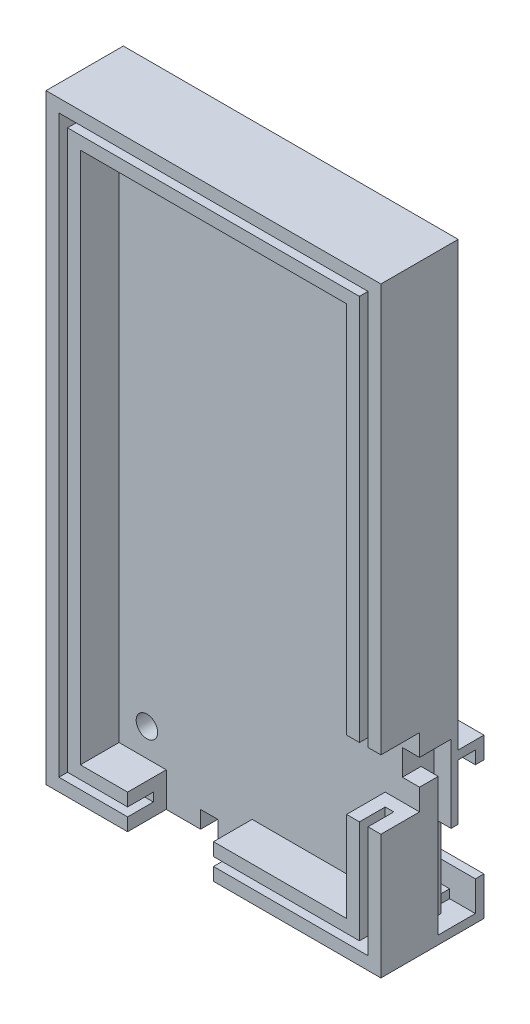
SolidWorks part; units mm, degrees
ref_plane "Front Plane" through (0, 0, 0) normal (0, 0, 1) x (1, 0, 0)
ref_plane "Top Plane" through (0, 0, 0) normal (0, 1, 0) x (1, 0, 0)
ref_plane "Right Plane" through (0, 0, 0) normal (1, 0, 0) x (0, 0, -1)
sketch "Sketch1" plane through (0, 0, 0) normal (0, 0, 1) x (1, 0, 0)
  line L1 (0, 0) -> (39, 0)
  line L2 (0, 0) -> (0, 70)
  line L3 (0, 70) -> (39, 70)
  line L4 (39, 0) -> (39, 70)
  dimension "D1" = 70
  dimension "D2" = 39
extrude "Boss-Extrude1" add sketch "Sketch1" along normal blind 4.5
sketch "Sketch2" plane through (0, 0, 4.5) normal (0, 0, 1) x (1, 0, 0)
  line L0 (0, 70) -> (0, 0) construction
  line L1 (39, 70) -> (0, 70)
  line L2 (39, 70) -> (39, 66)
  line L3 (39, 66) -> (0, 66)
  line L4 (0, 70) -> (0, 66)
  line L5 (0, 0) -> (39, 0) construction
  line L6 (0, 66) -> (4, 66)
  line L7 (0, 66) -> (0, 0)
  line L8 (0, 0) -> (4, 0)
  line L9 (4, 66) -> (4, 0)
  line L10 (39, 0) -> (39, 70) construction
  line L11 (4, 0) -> (39, 0)
  line L12 (4, 0) -> (4, 4)
  line L13 (4, 4) -> (39, 4)
  line L14 (39, 0) -> (39, 4)
  line L16 (39, 66) -> (35, 66)
  line L17 (39, 66) -> (39, 4)
  line L18 (39, 4) -> (35, 4)
  line L19 (35, 66) -> (35, 4)
  line M6 (0, 70) -> (0, 0)
  line M7 (0, 0) -> (39, 0)
  line M8 (39, 0) -> (39, 70)
  line M9 (39, 70) -> (0, 70)
  dimension "D1" = 4
  dimension "D2" = 4
  dimension "D3" = 4
  dimension "D4" = 4
extrude "Boss-Extrude2" add sketch "Sketch2" along normal blind 4.5 contours L3 M8 M9 M6 | L3 L19 L13 M8 | L9 L3 M6 M7 | L13 L9 M7 M8 region at (19.5, 68, 4.5) region at (37, 35, 4.5) region at (2, 33, 4.5) region at (21.5, 2, 4.5)
sketch "Sketch3" plane through (0, 4, 0) normal (0, 1, 0) x (1, 0, 0)
  line L0 (4, -4.5) -> (35, -4.5) construction
  line L1 (9.5, -4.5) -> (19.5, -4.5)
  line L2 (9.5, -4.5) -> (9.5, -9)
  line L3 (9.5, -9) -> (19.5, -9)
  line L4 (19.5, -4.5) -> (19.5, -9)
  line L5 (4, -9) -> (35, -9) construction
  line L6 (4, -9) -> (4, -4.5) construction
  dimension "D1" = 5.5
  dimension "D2" = 15.5
extrude "Cut-Extrude1" cut sketch "Sketch3" against normal blind 4
sketch "Sketch4" plane through (35, 0, 0) normal (-1, 0, 0) x (0, 0, 1)
  line L0 (4.5, 66) -> (4.5, 4) construction
  line L1 (4.5, 14.5) -> (9, 14.5)
  line L2 (4.5, 14.5) -> (4.5, 22.5)
  line L3 (4.5, 22.5) -> (9, 22.5)
  line L4 (9, 14.5) -> (9, 22.5)
  line L5 (9, 66) -> (9, 4) construction
  line L6 (9, 4) -> (4.5, 4) construction
  dimension "D1" = 10.5
  dimension "D2" = 18.5
extrude "Cut-Extrude2" cut sketch "Sketch4" against normal blind 4
sketch "Sketch5" plane through (0, 0, 4.5) normal (0, 0, 1) x (1, 0, 0)
  line L0 (4, 4) -> (9.5, 4) construction
  line L1 (4, 66) -> (4, 4) construction
  line L2 (19.5, 66) -> (19.5, 4) construction
  line L3 (35, 66) -> (4, 66) construction
  line L5 (19.5, 35) -> (4, 35) construction
  line L6 (4, 66) -> (4, 4) construction
  circle A0 centre (7.25, 7.25) radius 1.25
  circle A1 centre (31.75, 7.25) radius 1.25
  circle A2 centre (7.25, 62.75) radius 1.25
  dimension "D1" = 3.25
  dimension "D3" = 2.5
  dimension "D2" = 3.25
extrude "Cut-Extrude3" cut sketch "Sketch5" against normal blind 4
sketch "Sketch7" plane through (0, 0, 0) normal (0, 0, -1) x (-1, 0, 0)
  line L0 (-39, 0) -> (-39, 18.5) construction
  line L1 (-39, 0) -> (-39, 70) construction
  line L3 (-39, 1) -> (-8, 1)
  line L4 (-39, 1) -> (-39, 17.5)
  line L5 (-39, 17.5) -> (-8, 17.5)
  line L6 (-8, 1) -> (-8, 17.5)
  line L9 (0, 0) -> (-39, 0) construction
  line L10 (-39, 0) -> (-7, 0)
  line L11 (-7, 0) -> (-7, 18.5)
  line L12 (-7, 18.5) -> (-39, 18.5)
  line L13 (-39, 18.5) -> (-39, 17.5)
  line L14 (-39, 1) -> (-39, 0)
  line M8 (-39, 70) -> (-39, 0)
  line M9 (-39, 0) -> (0, 0)
  dimension "D1" = 18.5
  dimension "D2" = 1
  dimension "D3" = 16.5
  dimension "D4" = 31
  dimension "D5" = 32
  dimension "D6" = 18.5
extrude "Boss-Extrude3" add sketch "Sketch7" along normal blind 3 contours L11 L12 L5 L6 L3 M8 M9 region at (23.5, 0.6304, 0)
sketch "Sketch8" plane through (8, 0, 0) normal (1, 0, 0) x (0, 0, -1)
  line L0 (3, 17.5) -> (0, 17.5) construction
  line L1 (1, 17.5) -> (2, 17.5)
  line L2 (1, 17.5) -> (1, 16.5)
  line L3 (1, 16.5) -> (2, 16.5)
  line L4 (2, 17.5) -> (2, 16.5)
  line L5 (0, 1) -> (0, 17.5) construction
  line L6 (0, 9.25) -> (3, 9.25) construction
  line L7 (3, 1) -> (3, 17.5) construction
  line L8 (1, 2) -> (2, 2)
  line L9 (2, 1) -> (2, 2)
  line L10 (1, 1) -> (2, 1)
  line L11 (1, 1) -> (1, 2)
  dimension "D1" = 1
  dimension "D2" = 1
  dimension "D3" = 1
extrude "Boss-Extrude4" add sketch "Sketch8" along normal blind 28
sketch "Sketch9" plane through (8, 0, 0) normal (1, 0, 0) x (0, 0, -1)
  line L1 (3, 1) -> (2, 1)
  line L2 (3, 1) -> (3, 17.5)
  line L3 (3, 17.5) -> (2, 17.5)
  line L4 (2, 1) -> (2, 17.5)
extrude "Boss-Extrude5" add sketch "Sketch9" along normal blind 14
sketch "Sketch10" plane through (22, 0, 0) normal (1, 0, 0) x (0, 0, -1)
  line L0 (3, 1) -> (3, 17.5) construction
  line L1 (2, 17.5) -> (3, 17.5)
  line L2 (2, 17.5) -> (2, 16)
  line L3 (2, 16) -> (3, 16)
  line L4 (3, 17.5) -> (3, 16)
  line L6 (2, 1) -> (3, 1)
  line L7 (2, 1) -> (2, 4.5)
  line L8 (2, 4.5) -> (3, 4.5)
  line L9 (3, 1) -> (3, 4.5)
  dimension "D1" = 1.5
  dimension "D2" = 3.5
extrude "Boss-Extrude6" add sketch "Sketch10" along normal blind 17
sketch "Sketch11" plane through (0, 0, 0) normal (0, 0, -1) x (-1, 0, 0)
  line L0 (0, 0) -> (-7, 0) construction
  line L1 (-4, 0) -> (-5, 0)
  line L2 (-4, 0) -> (-4, 21.5)
  line L3 (-4, 21.5) -> (-5, 21.5)
  line L4 (-5, 0) -> (-5, 21.5)
  line L5 (-7, 0) -> (-7, 18.5) construction
  line L7 (0, 70) -> (0, 0) construction
  line L8 (-5, 21.5) -> (-22, 21.5)
  line L9 (-5, 21.5) -> (-5, 20.5)
  line L10 (-5, 20.5) -> (-22, 20.5)
  line L11 (-22, 21.5) -> (-22, 20.5)
  line L12 (-7, 18.5) -> (-39, 18.5) construction
  line L13 (-28, 18.5) -> (-27, 18.5)
  line L14 (-28, 18.5) -> (-28, 21.5)
  line L15 (-28, 21.5) -> (-27, 21.5)
  line L16 (-27, 18.5) -> (-27, 21.5)
  line M5 (-7, 0) -> (0, 0)
  line M9 (-39, 18.5) -> (-7, 18.5)
  dimension "D1" = 1
  dimension "D2" = 2
  dimension "D3" = 21.5
  dimension "D4" = 1
  dimension "D5" = 22
  dimension "D6" = 5
  dimension "D7" = 1
  dimension "D8" = 3
extrude "Boss-Extrude7" add sketch "Sketch11" along normal blind 3 contours L4 L2 L3 M5 | L8 L11 L10 L4 | L16 L15 L14 M9 region at (4.5, 10.75, 0) region at (13.5, 21, 0) region at (27.5, 20, 0)
sketch "Sketch12" plane through (0, 0, 0) normal (0, -1, 0) x (1, 0, 0)
  line L0 (19.5, 4.5) -> (9.5, 4.5) construction
  line L1 (5, 0) -> (15.5, 0)
  line L2 (5, 0) -> (5, 2)
  line L3 (5, 2) -> (15.5, 2)
  line L4 (15.5, 0) -> (15.5, 2)
  line L5 (9.5, 4.5) -> (9.5, 9) construction
  line L6 (13.5, 4.5) -> (15.5, 4.5)
  line L7 (13.5, 4.5) -> (13.5, 2)
  line L8 (13.5, 2) -> (15.5, 2)
  line L9 (15.5, 4.5) -> (15.5, 2)
  line L10 (19.5, 9) -> (19.5, 4.5) construction
  line M5 (19.5, 4.5) -> (9.5, 4.5)
  line M13 (5, 0) -> (7, 0)
  dimension "D1" = 2
  dimension "D2" = 4
  dimension "D3" = 4
  dimension "D4" = 0
extrude "Cut-Extrude4" cut sketch "Sketch12" against normal blind 2 contours L1 L4 L3 L2 M13 | L9 L7 L3 M5 region at (10.25, 0, 1) region at (14.5, 0, 3.25)
sketch "Sketch13" plane through (39, 0, 0) normal (1, 0, 0) x (0, 0, -1)
  line L0 (-4.5, 22.5) -> (-4.5, 14.5) construction
  line L1 (-4.5, 20) -> (-2.3266, 20)
  line L2 (-4.5, 20) -> (-4.5, 17)
  line L3 (-4.5, 17) -> (-2.3266, 17)
  line L4 (-2.3266, 20) -> (-2.3266, 17)
  line L5 (-9, 22.5) -> (-4.5, 22.5) construction
  line L6 (-4.5, 14.5) -> (-9, 14.5) construction
  line L7 (-2.3266, 17) -> (-2.3266, 11)
  line L8 (0, 1) -> (-2.3266, 1)
  line L9 (0, 1) -> (0, 11)
  line L10 (0, 11) -> (-2.3266, 11)
  line L11 (-2.3266, 1) -> (-2.3266, 11)
  line L18 (-2.3266, 11) -> (-0.8266, 11)
  line L19 (-2.3266, 11) -> (-2.3266, 20)
  line L20 (-2.3266, 20) -> (-0.8266, 20)
  line L21 (-0.8266, 11) -> (-0.8266, 20)
  line M19 (-4.5, 22.5) -> (-4.5, 14.5)
  line M27 (0, 1) -> (0, 17.5)
  dimension "D1" = 2.5
  dimension "D2" = 2.5
  dimension "D3" = 10
  dimension "D4" = 1.5
  dimension "D5" = 2.3266
extrude "Cut-Extrude5" cut sketch "Sketch13" against normal blind 2 contours L4 L1 L3 M19 | L10 L21 L20 L4 L7 | L11 L8 L10 M27 region at (39, 18.5, 3.4133) region at (39, 15.5, 1.5766) region at (39, 6, 1.1633)
sketch "Sketch14" plane through (0, 0, 9) normal (0, 0, 1) x (1, 0, 0)
  line L1 (1.5, 1.5) -> (2.5, 1.5)
  line L2 (1.5, 1.5) -> (1.5, 68.5)
  line L3 (1.5, 68.5) -> (2.5, 68.5)
  line L4 (2.5, 1.5) -> (2.5, 68.5)
  line L5 (0, 70) -> (0, 0) construction
  line L6 (4, 66) -> (4, 4) construction
  line L7 (39, 70) -> (0, 70) construction
  line L8 (35, 66) -> (4, 66) construction
  line L9 (2.5, 68.5) -> (37.5, 68.5)
  line L10 (2.5, 68.5) -> (2.5, 67.5)
  line L11 (2.5, 67.5) -> (37.5, 67.5)
  line L12 (37.5, 68.5) -> (37.5, 67.5)
  line L13 (39, 22.5) -> (39, 70) construction
  line L14 (19.5, 70) -> (19.5, 0) construction
  line L15 (0, 35) -> (39, 35) construction
  line L16 (37.5, 68.5) -> (36.5, 68.5)
  line L17 (36.5, 1.5) -> (36.5, 68.5)
  line L18 (37.5, 1.5) -> (36.5, 1.5)
  line L19 (37.5, 1.5) -> (37.5, 68.5)
  line L20 (2.5, 2.5) -> (37.5, 2.5)
  line L21 (37.5, 1.5) -> (37.5, 2.5)
  line L22 (2.5, 1.5) -> (37.5, 1.5)
  line L23 (2.5, 1.5) -> (2.5, 2.5)
  line M15 (35, 22.5) -> (39, 22.5)
  line M20 (9.5, 0) -> (9.5, 4)
  dimension "D2" = 1.5
  dimension "D3" = 1.5
  dimension "D4" = 1.5
  dimension "D5" = 1.5
extrude "Cut-Extrude6" cut sketch "Sketch14" against normal blind 3 contours L1 L4 L3 L2 | L4 L22 L20 M20 | L22 L17 L20 M20 | L20 L17 L18 L19 | L17 L20 L19 M15 | L19 L11 L17 M15 | L11 L17 L9 L4 | L17 L11 L12 L9 region at (2, 35, 9) region at (6, 2, 9) region at (23, 2, 9) region at (19.5, 68, 9) region at (37, 2, 9) region at (37, 68, 9) region at (37, 45, 9) region at (37, 12.5, 9)
